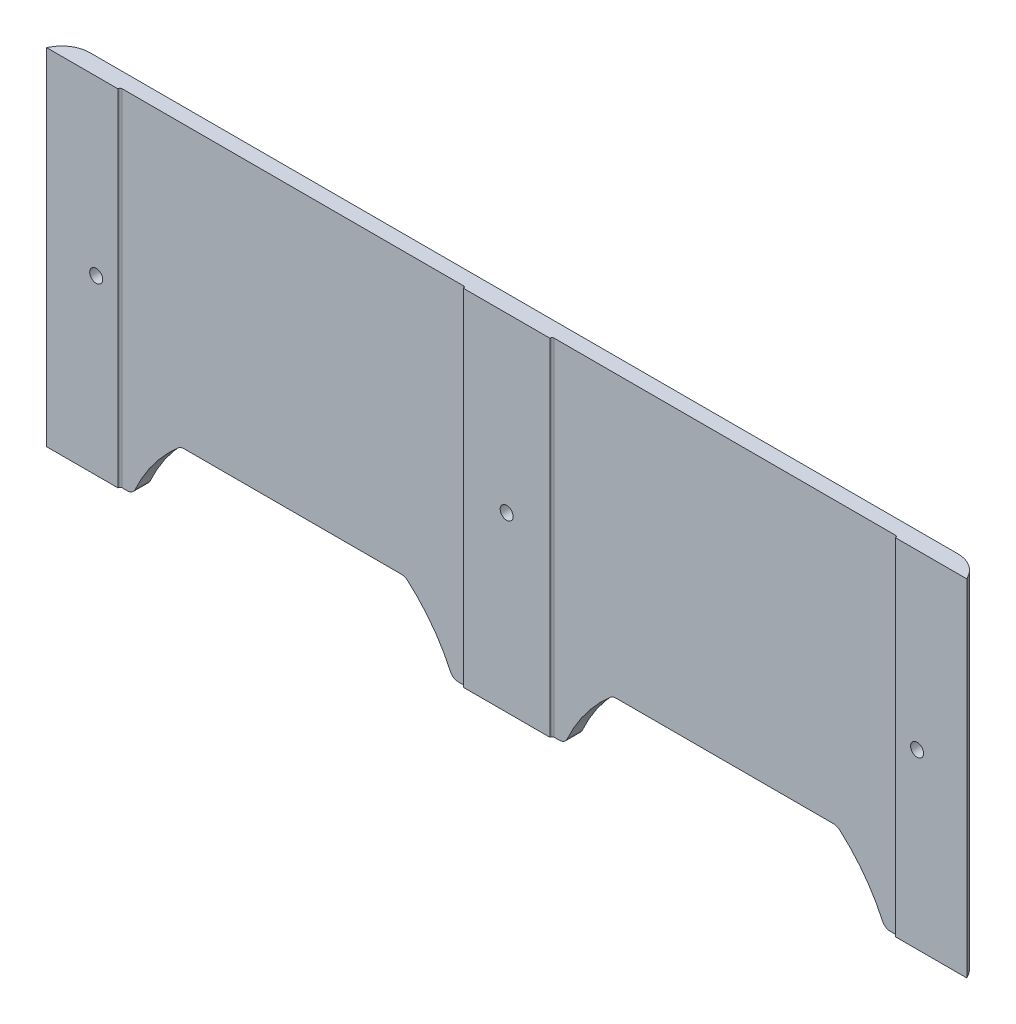
SolidWorks part; units mm, degrees
material "ABS PC"
ref_plane "Plan de face" through (0, 0, 0) normal (0, 0, 1) x (1, 0, 0)
ref_plane "Plan de dessus" through (0, 0, 0) normal (0, 1, 0) x (1, 0, 0)
ref_plane "Plan de droite" through (0, 0, 0) normal (1, 0, 0) x (0, 0, -1)
sketch "Esquisse1" plane through (0, 0, 0) normal (0, 0, 1) x (1, 0, 0)
  line L1 (-106.5, 0) -> (106.5, 0)
  line L2 (-106.5, 0) -> (-106.5, -80)
  line L3 (-106.5, -80) -> (106.5, -80)
  line L4 (106.5, 0) -> (106.5, -80)
  dimension "D1" = 213
  dimension "D2" = 80
extrude "Boss.-Extru.1" add sketch "Esquisse1" along normal blind 4
chamfer "Chanfrein1" distance 4 angle 30 2 edges at (-106.5, -40, 0) (106.5, -40, 0) first distance on face at (-106.5, -40, 2) first distance on face at (106.5, -40, 2)
fillet "Congé1" radius 6.5 2 edges at (-104.1906, -40, 0) (104.1906, -40, 0)
sketch "Esquisse2" plane through (0, 0, 0) normal (0, 0, -1) x (-1, 0, 0)
  line L1 (-100.4378, 0) -> (100.4378, 0) construction
  circle A1 centre (-95, -40) radius 1.5
  circle A4 centre (95, -40) radius 1.5
  circle A6 centre (0, -40) radius 1.5
  dimension "D1" = 3
  dimension "D2" = 95
  dimension "D4" = 190
  dimension "D5" = 40
extrude "Enlèv. mat.-Extru.1" cut sketch "Esquisse2" against normal through all
sketch "Esquisse3" plane through (0, 0, 0) normal (0, 1, 0) x (1, 0, 0)
  line L0 (-89.5, -4) -> (-10.5, -4) construction
  line L1 (106.5, -4) -> (-106.5, -4) construction
  line L2 (-89.5, -3.5) -> (-10.5, -3.5)
  line L3 (-89.5, -4.5) -> (-10.5, -4.5)
  line L4 (10.5, -4) -> (89.5, -4) construction
  line L5 (10.5, -3.5) -> (89.5, -3.5)
  line L6 (10.5, -4.5) -> (89.5, -4.5)
  line L7 (100.4378, 0) -> (-100.4378, 0) construction
  arc A0 (-89.5, -3.5) -> (-89.5, -4.5) centre (-89.5, -4) ccw
  arc A1 (-10.5, -4.5) -> (-10.5, -3.5) centre (-10.5, -4) ccw
  arc A2 (10.5, -3.5) -> (10.5, -4.5) centre (10.5, -4) ccw
  arc A3 (89.5, -4.5) -> (89.5, -3.5) centre (89.5, -4) ccw
  point P4 (-50, -4)
  point P11 (50, -4)
  point P19 (0, 0)
  dimension "D1" = 80
  dimension "D2" = 10
  dimension "D3" = 10
  dimension "D4" = 0.5
extrude "Enlèv. mat.-Extru.2" cut sketch "Esquisse3" against normal through all
chamfer "Chanfrein2" distance 1.5 angle 45 3 edges at (-93.5, -40, 0) (-1.5, -40, 0) (93.5, -40, 0)
sketch "Esquisse4" plane through (0, 0, 0) normal (0, 0, -1) x (-1, 0, 0)
  line L0 (-87, -80) -> (-13, -80)
  line L2 (-24.0801, -65) -> (-75.9199, -65)
  line L3 (-89.5, -80) -> (-10.5, -80) construction
  line L4 (-50, -65) -> (-50, -80) construction
  line L5 (0, 0) -> (0, -80) construction
  line L6 (-100.4378, 0) -> (100.4378, 0) construction
  line L7 (100.4378, -80) -> (-100.4378, -80) construction
  line L8 (87, -80) -> (13, -80)
  line L9 (24.0801, -65) -> (75.9199, -65)
  line L10 (-90, -80) -> (-90, 0) construction
  arc A0 (-13, -80) -> (-24.0801, -65) centre (-49, -95) ccw
  arc A1 (-87, -80) -> (-75.9199, -65) centre (-51, -95) cw
  arc A2 (87, -80) -> (75.9199, -65) centre (51, -95) ccw
  arc A3 (13, -80) -> (24.0801, -65) centre (49, -95) cw
  point P2 (-50, -80)
  dimension "D1" = 74
  dimension "D3" = 39
  dimension "D4" = 15
  dimension "D2" = 15
extrude "Enlèv. mat.-Extru.3" cut sketch "Esquisse4" against normal through all
fillet "Congé2" radius 2 8 edges at (-87, -80, 1.75) (-75.9199, -65, 1.75) (-24.0801, -65, 1.75) (-13, -80, 1.75) (13, -80, 1.75) (24.0801, -65, 1.75) (75.9199, -65, 1.75) (87, -80, 1.75)
